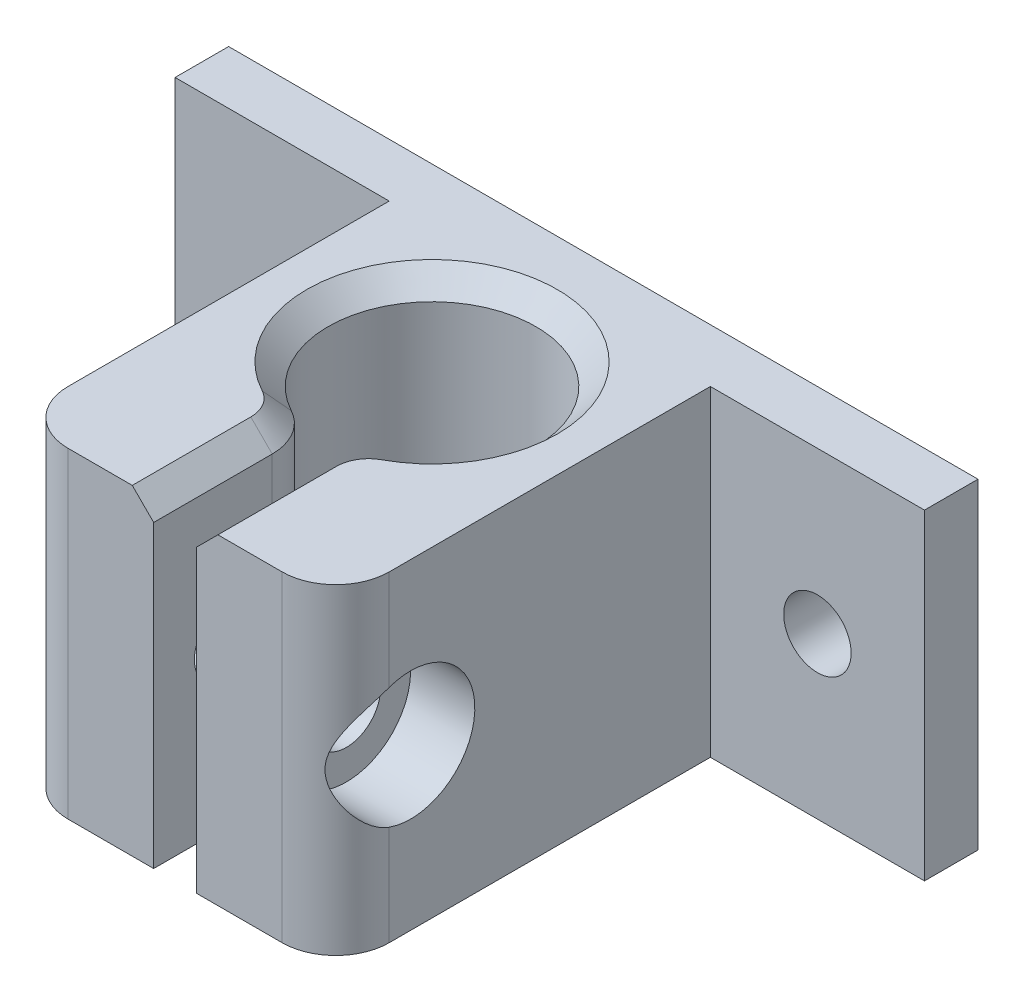
SolidWorks part; units mm, degrees
ref_plane "前视基准面" through (0, 0, 0) normal (0, 0, 1) x (1, 0, 0)
ref_plane "上视基准面" through (0, 0, 0) normal (0, 1, 0) x (1, 0, 0)
ref_plane "右视基准面" through (0, 0, 0) normal (1, 0, 0) x (0, 0, -1)
sketch "草图1" plane through (0, 0, 0) normal (0, 0, 1) x (1, 0, 0)
  line L1 (-35, -15) -> (35, -15)
  line L2 (-35, -15) -> (-35, 15)
  line L3 (-35, 15) -> (35, 15)
  line L4 (35, -15) -> (35, 15)
  line L5 (-35, -15) -> (35, 15) construction
  line L6 (-35, 15) -> (35, -15) construction
  point P0 (0, 0)
  dimension "D1" = 70
  dimension "D2" = 30
extrude "凸台-拉伸1" add sketch "草图1" along normal blind 5
sketch "草图2" plane through (0, 0, 5) normal (0, 0, 1) x (1, 0, 0)
  line L0 (35, 15) -> (-35, 15) construction
  circle A0 centre (-25, 0) radius 3.15
  circle A1 centre (25, 0) radius 3.15
  dimension "D1" = 6.3
  dimension "D2" = 6.3
  dimension "D3" = 15
  dimension "D4" = 50
  dimension "D5" = 25
extrude "切除-拉伸1" cut sketch "草图2" against normal blind 5
sketch "草图3" plane through (0, 0, 5) normal (0, 0, 1) x (1, 0, 0)
  line L0 (35, 15) -> (-35, 15) construction
  line L1 (-15, 15) -> (15, 15)
  line L2 (-15, 15) -> (-15, -15)
  line L3 (-15, -15) -> (15, -15)
  line L4 (15, 15) -> (15, -15)
  line L5 (-35, -15) -> (35, -15) construction
  line L6 (35, -15) -> (35, 15) construction
  dimension "D1" = 30
  dimension "D2" = 20
extrude "凸台-拉伸2" add sketch "草图3" along normal blind 35
sketch "草图4" plane through (0, 15, 0) normal (0, 1, 0) x (1, 0, 0)
  line L0 (15, -40) -> (15, -5) construction
  line L1 (35, 0) -> (-35, 0) construction
  circle A0 centre (0, -16) radius 9.7
  dimension "D1" = 19.4
  dimension "D2" = 15
  dimension "D3" = 16
extrude "切除-拉伸2" cut sketch "草图4" against normal blind 30
chamfer "倒角1" distance 5 angle 45 1 edges at (0, -15, 25.7)
sketch "草图5" plane through (0, 15, 0) normal (0, 1, 0) x (1, 0, 0)
  line L0 (15, -40) -> (-15, -40) construction
  line L1 (-2, -22) -> (2, -22)
  line L2 (-2, -22) -> (-2, -40)
  line L3 (-2, -40) -> (2, -40)
  line L4 (2, -22) -> (2, -40)
  line L5 (15, -40) -> (15, -5) construction
  line L6 (-15, -40) -> (-15, -5) construction
  dimension "D1" = 4
  dimension "D2" = 13
  dimension "D3" = 13
  dimension "D4" = 18
extrude "切除-拉伸3" cut sketch "草图5" against normal blind 30
fillet "圆角1" radius 5 2 edges at (2, 2.5, 25.4916) (-2, 2.5, 25.4916)
sketch "草图6" plane through (15, 0, 0) normal (1, 0, 0) x (0, 0, -1)
  line L0 (-40, -15) -> (-40, 15) construction
  line L1 (-40, 15) -> (-5, 15) construction
  circle A0 centre (-33, 0) radius 3.2
  dimension "D1" = 6.4
  dimension "D2" = 7
  dimension "D3" = 15
extrude "切除-拉伸4" cut sketch "草图6" against normal blind 30
sketch "草图7" plane through (15, 0, 0) normal (1, 0, 0) x (0, 0, -1)
  circle A0 centre (-33, 0) radius 6
  dimension "D1" = 12
extrude "切除-拉伸5" cut sketch "草图7" against normal blind 6
sketch "草图8" plane through (-15, 0, 0) normal (-1, 0, 0) x (0, 0, 1)
  line L1 (28, -2.8868) -> (33, -5.7735)
  line L2 (33, -5.7735) -> (38, -2.8868)
  line L3 (38, -2.8868) -> (38, 2.8868)
  line L4 (38, 2.8868) -> (33, 5.7735)
  line L5 (33, 5.7735) -> (28, 2.8868)
  line L6 (28, 2.8868) -> (28, -2.8868)
  circle A0 centre (33, 0) radius 5 construction
  dimension "D1" = 10
extrude "切除-拉伸6" cut sketch "草图8" against normal blind 6
fillet "圆角2" radius 5 2 edges at (-15, 0, 40) (15, 0, 40)
chamfer "倒角2" distance 2 angle 45 5 edges at (2, 15, 34.4632) (-2, 15, 34.4632) (2.7044, 15, 26.3675) (-2.7044, 15, 26.3675) (0, 15, 6.3)
